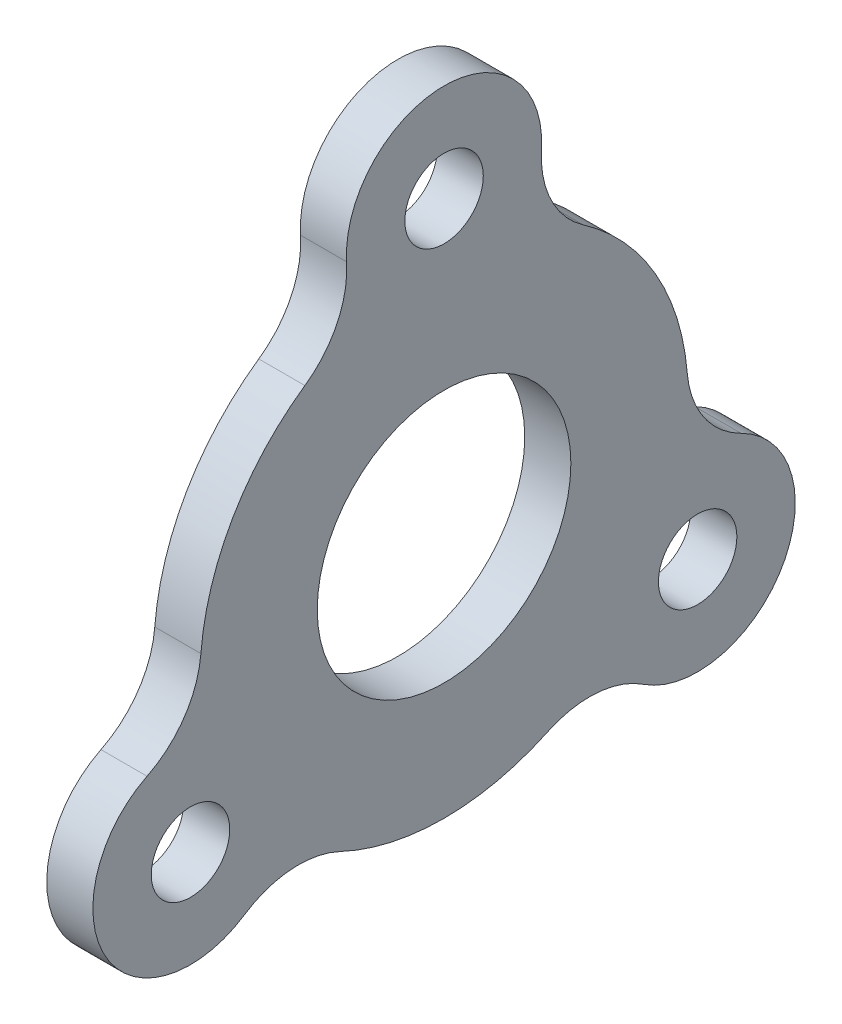
SolidWorks part; units mm, degrees
material "AR500"
ref_plane "Front Plane" through (0, 0, 0) normal (0, 0, 1) x (1, 0, 0)
ref_plane "Top Plane" through (0, 0, 0) normal (0, 1, 0) x (1, 0, 0)
ref_plane "Right Plane" through (0, 0, 0) normal (1, 0, 0) x (0, 0, -1)
sketch "Sketch1" plane through (0, 0, 0) normal (1, 0, 0) x (0, 0, -1)
  line L1 (0, 19.05) -> (-16.4978, -9.525) construction
  line L2 (-16.4978, -9.525) -> (16.4978, -9.525) construction
  line L3 (16.4978, -9.525) -> (0, 19.05) construction
  circle A0 centre (0, 0) radius 8.25
  arc A1 (-9.0537, 13.0402) -> (-15.82, 1.3206) centre (0, 0) ccw
  circle A2 centre (0, 19.05) radius 2.5527
  circle A3 centre (-16.4978, -9.525) radius 2.5527
  circle A4 centre (16.4978, -9.525) radius 2.5527
  arc A6 (-15.82, 1.3206) -> (-19.3229, -3.8381) centre (-22.148, 1.8489) cw
  arc A7 (-19.3229, -3.8381) -> (-12.9853, -14.8151) centre (-16.4978, -9.525) ccw
  arc A8 (-12.9853, -14.8151) -> (-6.7663, -14.3608) centre (-9.4728, -20.1051) cw
  circle A9 centre (0, 0) radius 19.05 construction
  arc A10 (9.0537, 13.0402) -> (6.3376, 18.6531) centre (12.6752, 18.2563) cw
  arc A11 (6.3376, 18.6531) -> (-6.3376, 18.6531) centre (0, 19.05) ccw
  arc A12 (-6.3376, 18.6531) -> (-9.0537, 13.0402) centre (-12.6752, 18.2563) cw
  arc A13 (6.7663, -14.3608) -> (12.9853, -14.8151) centre (9.4728, -20.1051) cw
  arc A14 (12.9853, -14.8151) -> (19.3229, -3.8381) centre (16.4978, -9.525) ccw
  arc A15 (19.3229, -3.8381) -> (15.82, 1.3206) centre (22.148, 1.8489) cw
  circle A16 centre (0, 19.05) radius 2.5527 construction
  arc A17 (15.82, 1.3206) -> (9.0537, 13.0402) centre (0, 0) ccw
  arc A19 (-6.7663, -14.3608) -> (6.7663, -14.3608) centre (0, 0) ccw
  point P35 (0, 0)
  dimension "D3" = 16.5
  dimension "D4" = 5.1054
  dimension "D5" = 6.35
  dimension "D6" = 6.35
  dimension "D7" = 15.875
  dimension "D2" = 3
extrude "Boss-Extrude1" add sketch "Sketch1" along normal blind 3
equation "\"D3@Sketch1\"=16.5mm"
